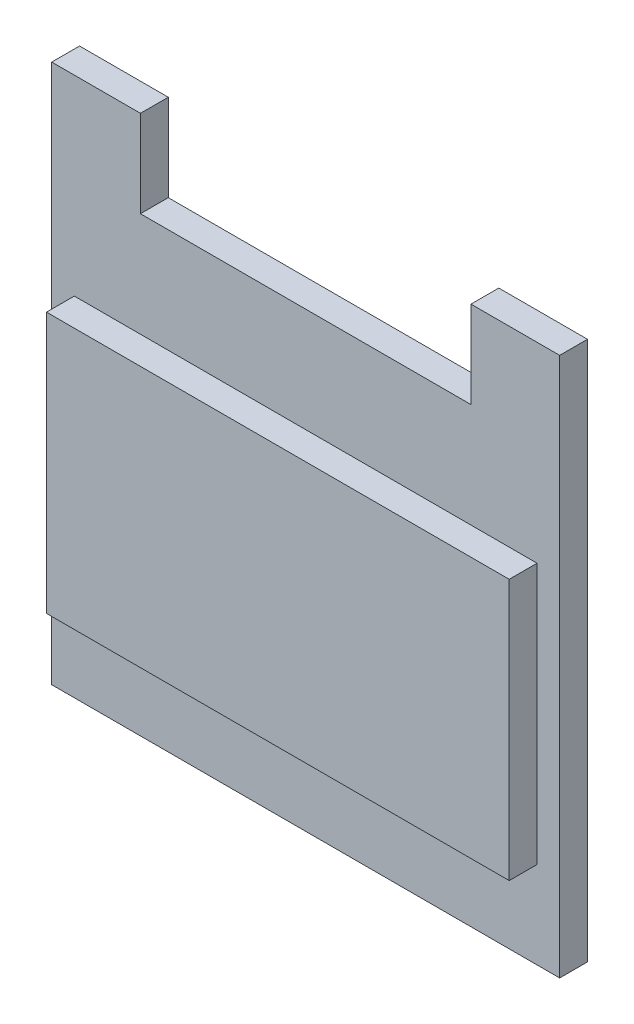
SolidWorks part; units mm, degrees
ref_plane "前视基准面" through (0, 0, 0) normal (0, 0, 1) x (1, 0, 0)
ref_plane "上视基准面" through (0, 0, 0) normal (0, 1, 0) x (1, 0, 0)
ref_plane "右视基准面" through (0, 0, 0) normal (1, 0, 0) x (0, 0, -1)
other "Configuration Table"
sketch "草图1" plane through (0, 0, 0) normal (0, 0, 1) x (1, 0, 0)
  line L0 (0.6744, 15.8034) -> (0.6744, -15.1966) construction
  line L1 (-13.9256, 15.8034) -> (15.2744, 15.8034)
  line L2 (-13.9256, 15.8034) -> (-13.9256, -15.1966)
  line L3 (-13.9256, -15.1966) -> (15.2744, -15.1966)
  line L4 (15.2744, 15.8034) -> (15.2744, -15.1966)
  line L5 (-12.6256, 4.8034) -> (13.9744, 4.8034)
  line L6 (-12.6256, 4.8034) -> (-12.6256, -10.1966)
  line L7 (-12.6256, -10.1966) -> (13.9744, -10.1966)
  line L8 (13.9744, 4.8034) -> (13.9744, -10.1966)
  line L9 (-9.3256, -12.0145) -> (10.6744, -12.0145)
  line L10 (-9.3256, -12.0145) -> (-9.3256, -14.0145)
  line L11 (-9.3256, -14.0145) -> (10.6744, -14.0145)
  line L12 (10.6744, -12.0145) -> (10.6744, -14.0145)
  line L13 (-8.8256, 15.8034) -> (10.1744, 15.8034)
  line L14 (-8.8256, 15.8034) -> (-8.8256, 10.8034)
  line L15 (-8.8256, 10.8034) -> (10.1744, 10.8034)
  line L16 (10.1744, 15.8034) -> (10.1744, 10.8034)
  line L17 (0.6744, 15.8034) -> (0.6744, 10.8034) construction
  dimension "D1" = 31
  dimension "D2" = 29.2
  dimension "D3" = 5
  dimension "D4" = 15
  dimension "D5" = 26.6
  dimension "D6" = 1.3
  dimension "D7" = 20
  dimension "D8" = 2
  dimension "D9" = 5
  dimension "D10" = 19
  dimension "D11" = 4.6
  dimension "D12" = 0
extrude "凸台-拉伸1" add sketch "草图1" along normal mid plane 3.2 contours L5 L8 L7 L6
extrude "凸台-拉伸2" add sketch "草图1<3>" against normal blind 1.6 separate body contours L12 L9 L10 L11 | L4 L1 L2 L3 L5 L8 L7 L6 L9 L12 L11 L10 region at (-11.3756, 15.3775, 0) region at (0.6744, -13.0145, 0)
sketch "草图1<3>" plane through (0, 0, 0) normal (0, 0, 1) x (1, 0, 0) same geometry as "草图1"
sketch "草图5" plane through (0, 0, 0) normal (0, 0, 1) x (1, 0, 0)
  line L0 (-9.3256, -12.0145) -> (-9.3256, -14.0145) construction
  line L1 (-9.3256, -14.0145) -> (10.6744, -14.0145) construction
  line L2 (10.6744, -12.0145) -> (10.6744, -14.0145) construction
  line L3 (-9.3256, -12.0145) -> (10.6744, -12.0145) construction
  line L4 (-9.3256, -12.0145) -> (-9.3256, -14.0145)
  line L5 (-9.3256, -14.0145) -> (10.6744, -14.0145)
  line L6 (10.6744, -12.0145) -> (10.6744, -14.0145)
  line L7 (-9.3256, -12.0145) -> (10.6744, -12.0145)
extrude "凸台-拉伸3" add sketch "草图5" against normal blind 4.1
sketch "草图6" plane through (0, 10.8034, 0) normal (0, 1, 0) x (1, 0, 0)
  line L0 (10.6744, 1.6) -> (-9.3256, 1.6) construction
  line L1 (-8.8256, 0) -> (10.1744, 0) construction
  line L2 (0.6744, 1.6) -> (0.6744, 0)
  line L3 (-8.8256, 1.6) -> (10.1744, 1.6) construction
  line L4 (0.6744, 0) -> (0.6744, -7.1004) construction
  point P0 (0.6744, 1.6)
  point P1 (0.6744, 0)
